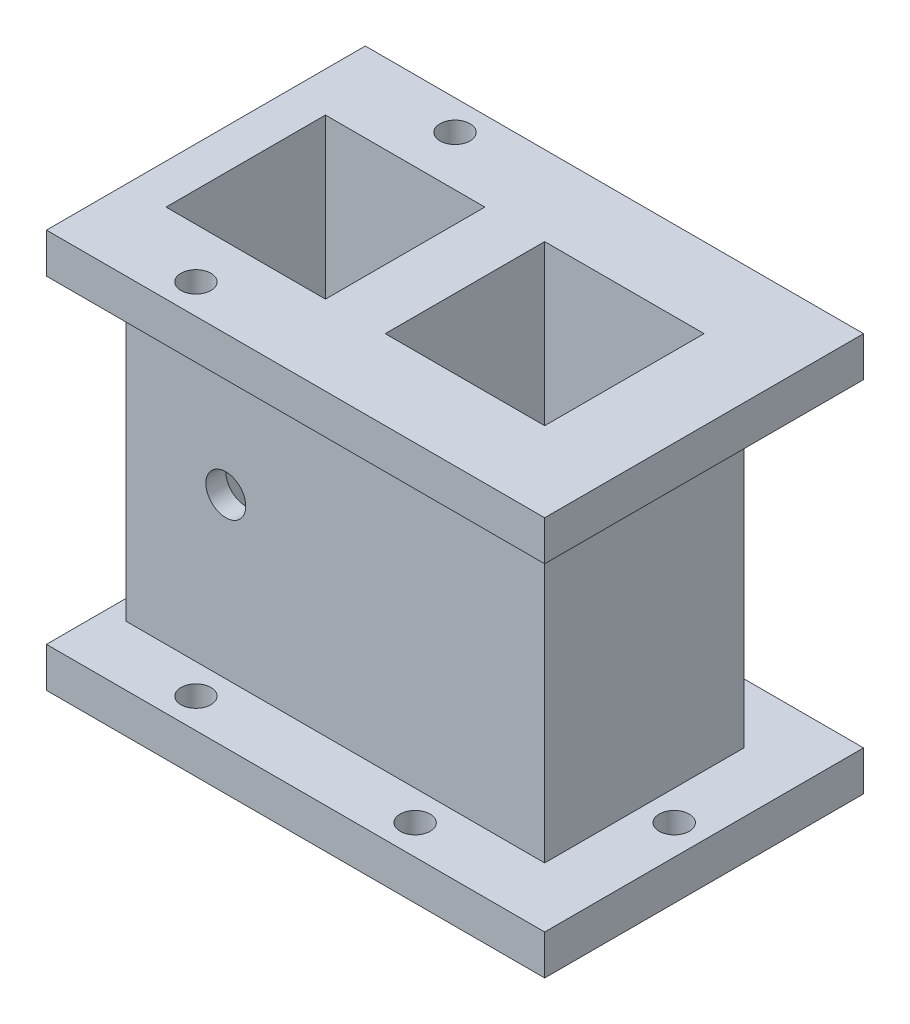
SolidWorks part; units mm, degrees
other "Markup1"
sketch "Sketch8" plane through (39.6875, 63.5, -25.4) normal (0.2237, 0.8347, -0.5032) x (-0.5017, -0.344, -0.7937)
material "PPS"
ref_plane "Front Plane" through (0, 0, 0) normal (0, 0, 1) x (1, 0, 0)
ref_plane "Top Plane" through (0, 0, 0) normal (0, 1, 0) x (1, 0, 0)
ref_plane "Right Plane" through (0, 0, 0) normal (1, 0, 0) x (0, 0, -1)
sketch "Sketch2" plane through (0, 0, 0) normal (0, 1, 0) x (1, 0, 0)
  line L1 (-39.6875, -25.4) -> (39.6875, -25.4)
  line L2 (-39.6875, -25.4) -> (-39.6875, 25.4)
  line L3 (-39.6875, 25.4) -> (39.6875, 25.4)
  line L4 (39.6875, -25.4) -> (39.6875, 25.4)
  line L5 (-39.6875, -25.4) -> (39.6875, 25.4) construction
  line L6 (-39.6875, 25.4) -> (39.6875, -25.4) construction
  point P0 (0, 0)
  dimension "D1" = 50.8
  dimension "D2" = 79.375
extrude "Boss-Extrude1" add sketch "Sketch2" along normal blind 6.35 contours L4 L3 L2 L1
sketch "Sketch3" plane through (0, 6.35, 0) normal (0, 1, 0) x (1, 0, 0)
  line L0 (-39.6875, -25.4) -> (-39.6875, 25.4) construction
  line L1 (-33.3375, -12.7) -> (-7.9375, -12.7)
  line L2 (-33.3375, -12.7) -> (-33.3375, 12.7)
  line L3 (-33.3375, 12.7) -> (-7.9375, 12.7)
  line L4 (-7.9375, -12.7) -> (-7.9375, 12.7)
  line L5 (-33.3375, -12.7) -> (-7.9375, 12.7) construction
  line L6 (-33.3375, 12.7) -> (-7.9375, -12.7) construction
  line L7 (-39.6875, 0) -> (39.6875, 0) construction
  line L8 (1.5875, 12.7) -> (26.9875, 12.7)
  line L9 (1.5875, 12.7) -> (1.5875, -12.7)
  line L10 (1.5875, -12.7) -> (26.9875, -12.7)
  line L11 (26.9875, 12.7) -> (26.9875, -12.7)
  line L12 (1.5875, 12.7) -> (26.9875, -12.7) construction
  line L13 (1.5875, -12.7) -> (26.9875, 12.7) construction
  line L14 (39.6875, -25.4) -> (39.6875, 25.4) construction
  line L16 (-36.5125, -15.875) -> (30.1625, -15.875)
  line L17 (-36.5125, -15.875) -> (-36.5125, 15.875)
  line L18 (-36.5125, 15.875) -> (30.1625, 15.875)
  line L19 (30.1625, -15.875) -> (30.1625, 15.875)
  point P0 (-20.6375, 0)
  point P7 (14.2875, 0)
  dimension "D1" = 25.4
  dimension "D2" = 25.4
  dimension "D3" = 6.35
  dimension "D4" = 25.4
  dimension "D5" = 25.4
  dimension "D6" = 12.7
  dimension "D7" = 3.175
  dimension "D8" = 3.175
  dimension "D9" = 3.175
  dimension "D10" = 3.175
extrude "Boss-Extrude3" add sketch "Sketch3" along normal blind 50.8
sketch "Sketch4" plane through (0, 57.15, 0) normal (0, 1, 0) x (1, 0, 0)
  line L1 (-33.3375, 12.7) -> (-7.9375, 12.7)
  line L2 (-33.3375, 12.7) -> (-33.3375, -12.7)
  line L3 (-33.3375, -12.7) -> (-7.9375, -12.7)
  line L4 (-7.9375, 12.7) -> (-7.9375, -12.7)
  line L5 (1.5875, 12.7) -> (26.9875, 12.7)
  line L6 (1.5875, 12.7) -> (1.5875, -12.7)
  line L7 (1.5875, -12.7) -> (26.9875, -12.7)
  line L8 (26.9875, 12.7) -> (26.9875, -12.7)
ref_plane "Plane1" through (0, 31.75, 0) normal (0, 1, 0) x (1, 0, 0)
mirror "Mirror1" about plane through (0, 31.75, 0) normal (0, 1, 0) of "Boss-Extrude1"
extrude "Cut-Extrude4" cut sketch "Sketch4" against normal through all both and the other way through all
sketch "Sketch5" plane through (0, 0, 15.875) normal (0, 0, 1) x (1, 0, 0)
  line L0 (-36.5125, 31.75) -> (30.1625, 31.75) construction
  line L1 (-33.3375, 44.8114) -> (-7.9375, 44.8114) construction
  line L3 (-36.5125, 57.15) -> (-36.5125, 6.35) construction
  line L4 (30.1625, 57.15) -> (30.1625, 6.35) construction
  line L5 (-33.3375, 57.15) -> (-33.3375, 6.35) construction
  line L6 (-36.5125, 57.15) -> (30.1625, 57.15) construction
  line L7 (-36.5125, 6.35) -> (30.1625, 6.35) construction
  line L8 (-7.9375, 57.15) -> (-7.9375, 6.35) construction
  circle A0 centre (-20.6375, 31.75) radius 3.175
  dimension "D1" = 6.35
  dimension "D2" = 3.175
  dimension "D3" = 25.4
  dimension "D4" = 12.7
extrude "Cut-Extrude5" cut sketch "Sketch5" against normal through all
sketch "Sketch6" plane through (0, 6.35, 0) normal (0, 1, 0) x (1, 0, 0)
  line L0 (30.1625, 0) -> (39.6875, 0) construction
  line L1 (30.1625, -15.875) -> (30.1625, 15.875) construction
  line L2 (39.6875, -25.4) -> (39.6875, 25.4) construction
  circle A0 centre (34.925, 0) radius 2.3876
  point P8 (0, 0)
  point P9 (0, 0)
  dimension "D1" = 4.7752
ref_plane "Plane2" through (14.2875, 0, 0) normal (1, 0, 0) x (0, 0, -1)
ref_plane "Plane3" through (0, 0, 0) normal (0, 0, 1) x (1, 0, 0)
ref_axis "Axis1" through (14.2875, -3.175, 0) along (0, 1, 0)
extrude "Cut-Extrude6" cut sketch "Sketch6" against normal through all
pattern_circular "CirPattern1" count 4 over 360 about axis through (14.2875, -3.175, 0) along (0, 1, 0) skipping 2 of "Cut-Extrude6"
sketch "Sketch7" plane through (0, 6.35, 0) normal (0, 1, 0) x (1, 0, 0)
  line L0 (-33.3375, -17.2263) -> (-33.3375, -22.8133) construction
  line L5 (-39.6875, -25.4) -> (-39.6875, 25.4) construction
  line L6 (-7.9375, -17.2263) -> (-7.9375, -22.8133) construction
  line L7 (-7.9375, -20.6375) -> (-33.3375, -20.6375) construction
  circle A1 centre (-20.6375, -20.6375) radius 2.3876
  point P10 (0, 0)
  dimension "D3" = 4.7752
  dimension "D1" = 6.35
  dimension "D2" = 25.4
extrude "Cut-Extrude7" cut sketch "Sketch7" against normal through all both and the other way through all
mirror "Mirror2" about plane through (0, 0, 0) normal (0, 0, 1) of "Cut-Extrude7"
scale "Scale1" scale about centroid uniform scaling yes scale factor 1.02
